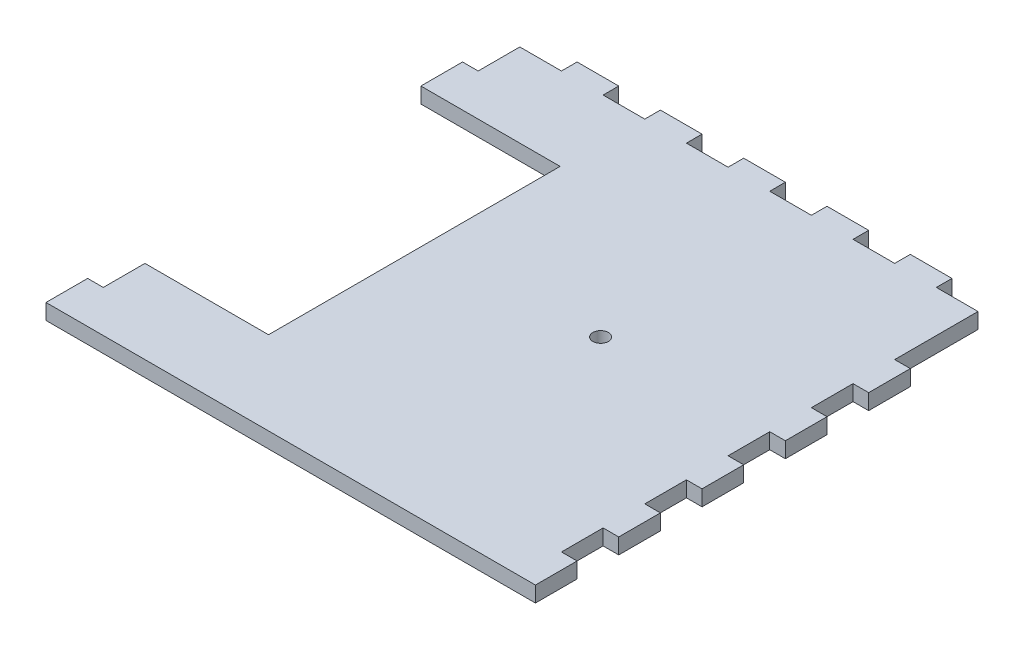
SolidWorks part; units mm, degrees
ref_plane "Front Plane" through (0, 0, 0) normal (0, 0, 1) x (1, 0, 0)
ref_plane "Top Plane" through (0, 0, 0) normal (0, 1, 0) x (1, 0, 0)
ref_plane "Right Plane" through (0, 0, 0) normal (1, 0, 0) x (0, 0, -1)
sketch "Sketch1" plane through (0, 0, 0) normal (0, 1, 0) x (1, 0, 0)
  line L1 (-139.7, -139.7) -> (139.7, -139.7)
  line L2 (-139.7, -139.7) -> (-139.7, 139.7)
  line L3 (-139.7, 139.7) -> (139.7, 139.7)
  line L4 (139.7, -139.7) -> (139.7, 139.7)
  line L5 (-139.7, -139.7) -> (139.7, 139.7) construction
  line L6 (-139.7, 139.7) -> (139.7, -139.7) construction
  point P0 (0, 0)
  dimension "D1" = 279.4
  dimension "D2" = 279.4
extrude "Boss-Extrude1" add sketch "Sketch1" along normal blind 9.525
sketch "Sketch2" plane through (139.7, 0, 0) normal (1, 0, 0) x (0, 0, -1)
  line L0 (-139.7, 9.525) -> (139.7, 9.525) construction
  line L1 (-139.7, 0) -> (-114.3, 0)
  line L2 (-139.7, 0) -> (-139.7, 9.525)
  line L3 (-139.7, 9.525) -> (-114.3, 9.525)
  line L4 (-114.3, 0) -> (-114.3, 9.525)
  dimension "D1" = 25.4
extrude "Boss-Extrude2" add sketch "Sketch2" along normal blind 9.525
pattern_linear "LPattern1" count 5 spacing 50.8 along (0, 0, -1) of "Boss-Extrude2"
mirror "Mirror1" about plane through (0, 0, 0) normal (1, 0, 0) of "LPattern1"
sketch "Sketch3" plane through (0, 0, -139.7) normal (0, 0, -1) x (-1, 0, 0)
  line L0 (-139.7, 9.525) -> (139.7, 9.525) construction
  line L1 (-114.3, 9.525) -> (-88.9, 9.525)
  line L2 (-114.3, 9.525) -> (-114.3, 0)
  line L3 (-114.3, 0) -> (-88.9, 0)
  line L4 (-88.9, 9.525) -> (-88.9, 0)
  line L5 (-139.7, 0) -> (139.7, 0) construction
  line L7 (-149.225, 0) -> (-149.225, 9.525) construction
  dimension "D1" = 34.925
  dimension "D2" = 25.4
extrude "Boss-Extrude3" add sketch "Sketch3" along normal blind 9.525
pattern_linear "LPattern2" count 5 spacing 50.8 along (-1, 0, 0) of "Boss-Extrude3"
sketch "Sketch6" plane through (0, 9.525, 0) normal (0, 1, 0) x (1, 0, 0)
  line L0 (63.5, 139.7) -> (38.1, 139.7) construction
  line L1 (139.7, -12.7) -> (139.7, 12.7) construction
  circle A0 centre (38.1, 11.176) radius 4.7625
  dimension "D1" = 128.524
  dimension "D3" = 9.525
  dimension "D2" = 101.6
extrude "Cut-Extrude1" cut sketch "Sketch6" against normal through all
sketch "Sketch8" plane through (0, 9.525, 0) normal (0, 1, 0) x (1, 0, 0)
  line L1 (-149.225, 88.9) -> (-64.3339, 88.9)
  line L2 (-149.225, 88.9) -> (-149.225, -88.9)
  line L3 (-149.225, -88.9) -> (-64.3339, -88.9)
  line L4 (-64.3339, 88.9) -> (-64.3339, -88.9)
  dimension "D1" = 177.8
extrude "Cut-Extrude3" cut sketch "Sketch8" against normal through all
sketch "Sketch7" plane through (0, 9.525, 0) normal (0, 1, 0) x (1, 0, 0)
  line L2 (-114.3, 139.7) -> (-139.7, 139.7) construction
  line L3 (-139.7, 139.7) -> (-139.7, 88.9) construction
  circle A0 centre (-101.6, 65.278) radius 5.08
  circle A1 centre (-101.6, 27.686) radius 5.08
  dimension "D1" = 10.16
  dimension "D2" = 10.16
  dimension "D3" = 38.1
  dimension "D5" = 37.592
  dimension "D6" = 74.422
sketch "Sketch9" plane through (-139.7, 0, 0) normal (-1, 0, 0) x (0, 0, 1)
  line L0 (153.67, 0) -> (-153.67, 0) construction
  line L1 (-88.9, 9.525) -> (-114.3, 9.525)
  line L2 (-88.9, 9.525) -> (-88.9, 0)
  line L3 (-88.9, 0) -> (-114.3, 0)
  line L4 (-114.3, 9.525) -> (-114.3, 0)
  dimension "D1" = 25.4
extrude "Boss-Extrude4" add sketch "Sketch9" along normal blind 9.525
